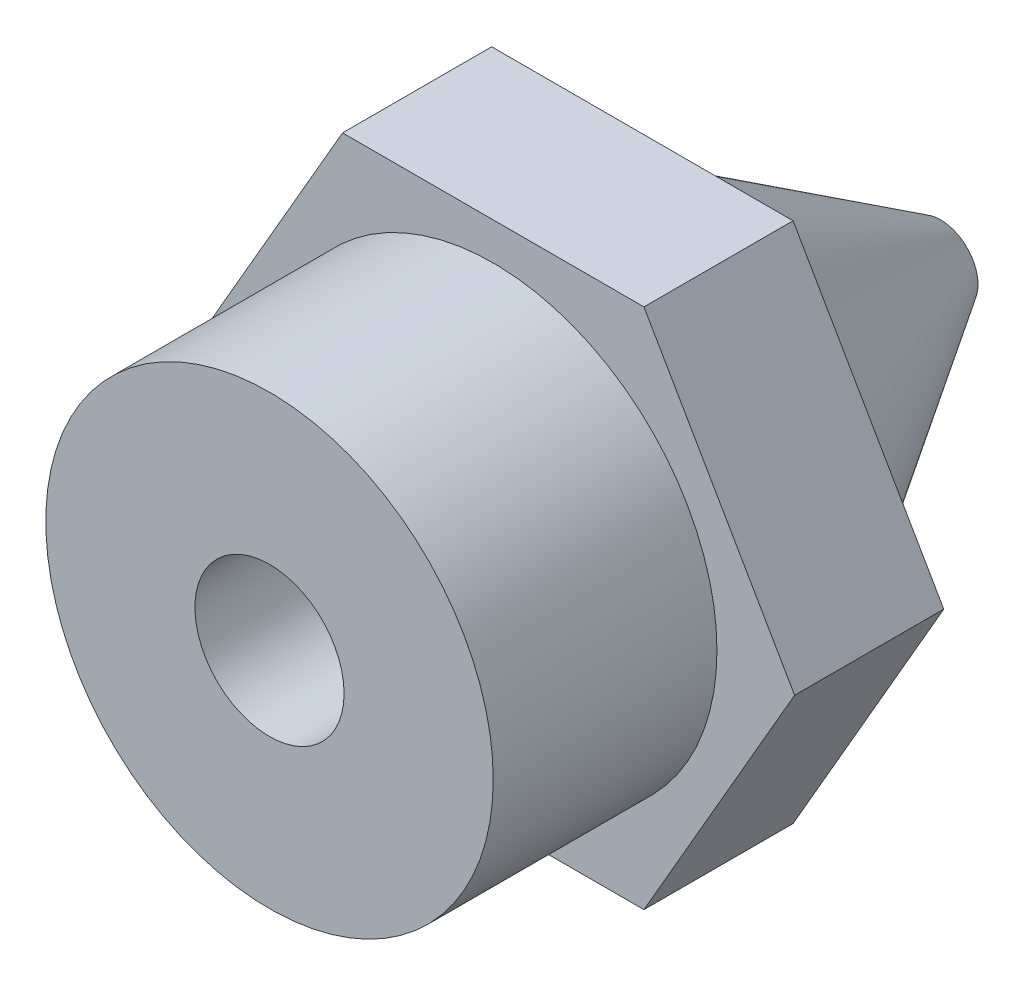
SolidWorks part; units mm, degrees
ref_plane "Plan de face" through (0, 0, 0) normal (0, 0, 1) x (1, 0, 0)
ref_plane "Plan de dessus" through (0, 0, 0) normal (0, 1, 0) x (1, 0, 0)
ref_plane "Plan de droite" through (0, 0, 0) normal (1, 0, 0) x (0, 0, -1)
sketch "Esquisse1" plane through (0, 0, 0) normal (0, 0, 1) x (1, 0, 0)
  line L1 (4.0415, 0) -> (2.0207, 3.5)
  line L2 (2.0207, 3.5) -> (-2.0207, 3.5)
  line L3 (-2.0207, 3.5) -> (-4.0415, 0)
  line L4 (-4.0415, 0) -> (-2.0207, -3.5)
  line L5 (-2.0207, -3.5) -> (2.0207, -3.5)
  line L6 (2.0207, -3.5) -> (4.0415, 0)
  circle A0 centre (0, 0) radius 3.5 construction
  dimension "D1" = 7
extrude "Boss.-Extru.1" add sketch "Esquisse1" along normal blind 9
sketch "Esquisse2" plane through (0, 0, 9) normal (0, 0, 1) x (1, 0, 0)
  line L1 (-7.9912, 5.5023) -> (7.566, 5.5023)
  line L2 (-7.9912, 5.5023) -> (-7.9912, -5.9665)
  line L3 (-7.9912, -5.9665) -> (7.566, -5.9665)
  line L4 (7.566, 5.5023) -> (7.566, -5.9665)
  circle A0 centre (0, 0) radius 3
  dimension "D1" = 6
extrude "Enlèv. mat.-Extru.1" cut sketch "Esquisse2" against normal blind 3
cosmetic thread "Représentation de filetage1" parameters "D2"=4.891
sketch "Esquisse3" plane through (0, 0, 0) normal (0, 0, -1) x (-1, 0, 0)
  line L1 (7.8656, -6.0768) -> (-7.4574, -6.0768)
  line L2 (7.8656, -6.0768) -> (7.8656, 5.7844)
  line L3 (7.8656, 5.7844) -> (-7.4574, 5.7844)
  line L4 (-7.4574, -6.0768) -> (-7.4574, 5.7844)
  circle A0 centre (0, 0) radius 3
  dimension "D1" = 6
extrude "Enlèv. mat.-Extru.3" cut sketch "Esquisse3" against normal blind 4
chamfer "Chanfrein2" distance 4 angle 32 1 edges at (-3, 0, 0) first distance on face at (-3, 0, 4)
sketch "Esquisse4" plane through (0, 0, 0) normal (0, 1, 0) x (1, 0, 0)
  line L0 (0, -10.6849) -> (0, 1.9802) construction
  line L1 (0.5005, 0) -> (-0.5005, 0) construction
  line L2 (-3, -9) -> (3, -9) construction
  line L3 (0, 0) -> (0.2, 0)
  line L4 (0.2, 0) -> (0.2, -0.5)
  line L5 (0, -9) -> (0, 0)
  line L6 (0, -9) -> (1, -9)
  line L7 (1, -9) -> (1, -1.6425)
  line L8 (0.2, -0.5) -> (1, -1.6425)
revolve "Enlèvement de matière-Révolution1" cut sketch "Esquisse4" angle 360 about L0
chamfer "Chanfrein3" [suppressed] distance 0.5 angle 45
